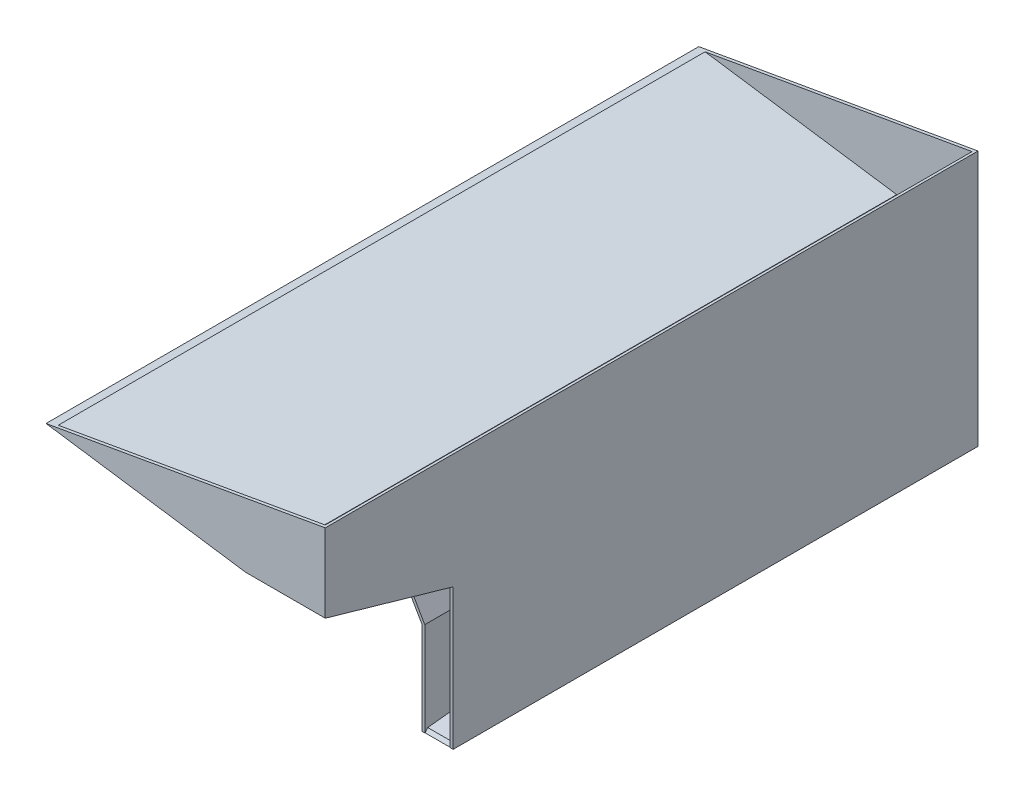
SolidWorks part; units mm, degrees
ref_plane "Front Plane" through (0, 0, 0) normal (0, 0, 1) x (1, 0, 0)
ref_plane "Top Plane" through (0, 0, 0) normal (0, 1, 0) x (1, 0, 0)
ref_plane "Right Plane" through (0, 0, 0) normal (1, 0, 0) x (0, 0, -1)
other "Center of Mass"
sketch "Sketch2" plane through (0, 0, 0) normal (0, 0, 1) x (1, 0, 0)
  line L0 (0, 0) -> (-105, 181.8653)
  line L1 (-105, 181.8653) -> (-532.9388, 244.1441)
  line L2 (-532.9388, 244.1441) -> (67.4, 350)
  line L3 (67.4, 350) -> (67.4, -200)
  line L4 (67.4, -200) -> (0, -200)
  line L5 (0, -200) -> (0, 0)
  dimension "D1" = 150
  dimension "D2" = 609.6
  dimension "D3" = 550
  dimension "D4" = 200
  dimension "D5" = 67.4
  dimension "D6" = 210
  dimension "D7" = 280
extrude "Boss-Extrude1" add sketch "Sketch2" along normal mid plane 1403.35
shell "Shell1" thickness 6.35 removed face at (-232.7694, 297.072, 0)
sketch "Sketch3" plane through (0, 0, 701.675) normal (0, 0, 1) x (1, 0, 0)
  line L1 (12.7, -187.3) -> (54.7, -187.3)
  line L2 (12.7, -187.3) -> (12.7, 102.7)
  line L3 (12.7, 102.7) -> (54.7, 102.7)
  line L4 (54.7, -187.3) -> (54.7, 102.7)
  line L6 (0, -200) -> (67.4, -200) construction
  point P6 (33.7, -200)
  point P7 (33.7, -187.3)
  dimension "D1" = 42
  dimension "D2" = 12.7
  dimension "D3" = 290
extrude "Cut-Extrude1" cut sketch "Sketch3" against normal blind 20
scale "Scale1" [suppressed]
sketch "Sketch6" plane through (0, 0, 701.675) normal (0, 0, 1) x (1, 0, 0)
  line L1 (-167.2364, 157.2102) -> (-3.283, 157.2102)
  line L2 (-167.2364, 157.2102) -> (-167.2364, -5.4179)
  line L3 (-167.2364, -5.4179) -> (-3.283, -5.4179)
  line L4 (-3.283, 157.2102) -> (-3.283, -5.4179)
extrude "Cut-Extrude3" [suppressed] cut sketch "Sketch6" against normal blind 200
sketch "Sketch7" plane through (0, 0, 0) normal (-1, 0, 0) x (0, 0, 1)
  line L1 (701.675, -200) -> (426.675, -200)
  line L2 (701.675, -200) -> (701.675, 102.7)
  line L3 (701.675, 102.7) -> (426.675, 102.7)
  line L4 (426.675, -200) -> (426.675, 102.7)
  dimension "D1" = 275
  dimension "D2" = 302.7
extrude "Cut-Extrude5" cut sketch "Sketch7" against normal mid plane 200
sketch "Sketch9" plane through (67.4, 0, 0) normal (1, 0, 0) x (0, 0, -1)
  line L0 (-701.675, 102.7) -> (-701.675, 350) construction
  line L1 (-426.675, 102.7) -> (-701.675, 102.7)
  line L2 (-426.675, 102.7) -> (-426.675, 181.7)
  line L3 (-426.675, 181.7) -> (-701.675, 181.7)
  line L4 (-701.675, 102.7) -> (-701.675, 181.7)
  line L5 (-701.675, 181.7) -> (-426.675, 102.7)
  line M2 (-701.675, 102.7) -> (-426.675, 102.7)
  line M7 (-701.675, 350) -> (-701.675, 102.7)
  dimension "D1" = 79
extrude "Cut-Extrude7" cut sketch "Sketch9" against normal through all contours L5 M7 M2 region at (67.4, 129.0333, 610.0083)
sketch "Sketch11" plane through (0, -18.3572, 5.2735) normal (0, -0.9611, 0.2761) x (1, 0, 0)
  line L0 (67.4, 724.5674) -> (67.4, 438.445)
  line L1 (67.4, 438.445) -> (-59.2939, 438.445)
  line L2 (-59.2939, 438.445) -> (-104.9045, 724.5674)
  line L3 (-104.9045, 724.5674) -> (67.4, 724.5674)
extrude "Boss-Extrude3" add sketch "Sketch11" against normal blind 6.35
sketch "Sketch12" plane through (6.35, 0, 0) normal (1, 0, 0) x (0, 0, -1)
  line L0 (-426.675, -193.65) -> (688.975, -76.3905)
  line L1 (688.975, -76.3905) -> (688.975, -193.65)
  line L2 (688.975, -193.65) -> (-426.675, -193.65)
  line L3 (701.675, -200) -> (701.675, 350) construction
  dimension "D1" = 6.35
  dimension "D2" = 12.7
  dimension "D3" = 6
extrude "Boss-Extrude4" add sketch "Sketch12" along normal up to surface (54.7 mm away) up to face at (61.05, 101.2066, 182.6102)
chamfer "Chamfer1" distance 6.35 angle 45 1 edges at (33.7, -193.65, 426.675) first distance on face at (33.7, -135.0202, -131.15)
